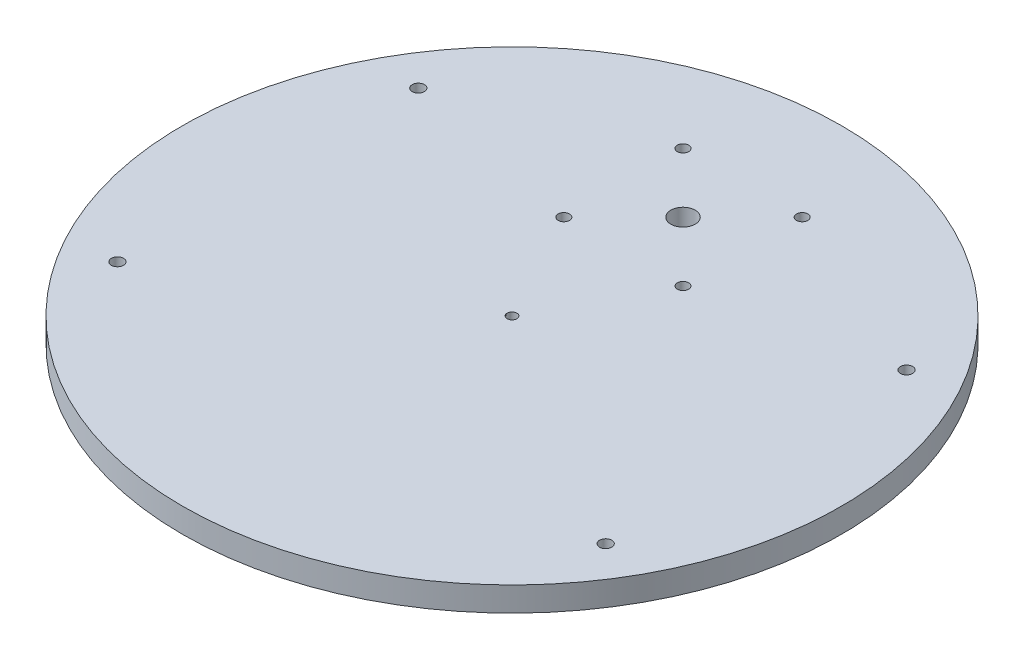
SolidWorks part; units mm, degrees
ref_plane "Front Plane" through (0, 0, 0) normal (0, 0, 1) x (1, 0, 0)
ref_plane "Top Plane" through (0, 0, 0) normal (0, 1, 0) x (1, 0, 0)
ref_plane "Right Plane" through (0, 0, 0) normal (1, 0, 0) x (0, 0, -1)
sketch "Sketch1" plane through (0, 0, 0) normal (0, 1, 0) x (1, 0, 0)
  circle A0 centre (0, 0) radius 85.725
  dimension "D1" = 171.45
extrude "Boss-Extrude1" add sketch "Sketch1" along normal blind 6.35
sketch "Sketch2" plane through (0, 6.35, 0) normal (0, 1, 0) x (1, 0, 0)
  line L0 (-63.5, 39.1325) -> (-63.5, -39.1325) construction
  line L1 (-63.5, -39.1325) -> (63.5, -39.1325) construction
  line L2 (63.5, -39.1325) -> (63.5, 39.1325) construction
  line L3 (63.5, 39.1325) -> (-63.5, 39.1325) construction
  circle A0 centre (-63.5, 39.1325) radius 1.5875
  circle A1 centre (63.5, 39.1325) radius 1.5875
  circle A2 centre (-63.5, -39.1325) radius 1.5875
  circle A3 centre (63.5, -39.1325) radius 1.5875
  dimension "D1" = 3.175
  dimension "D2" = 3.175
  dimension "D3" = 127
  dimension "D4" = 3.175
  dimension "D5" = 3.175
  dimension "D6" = 78.265
  dimension "D8" = 39.1325
  dimension "D9" = 63.5
extrude "Cut-Extrude1" cut sketch "Sketch2" against normal up to next
sketch "Sketch3" plane through (0, 6.35, 0) normal (0, 1, 0) x (1, 0, 0)
  line L0 (0, 44.4822) -> (0, 0) construction
  circle A0 centre (0, 44.4822) radius 3.175
  dimension "D1" = 6.35
  dimension "D2" = 44.4822
extrude "Cut-Extrude2" cut sketch "Sketch3" against normal up to next contours A0
ref_axis "Axis1" through (0, 6.35, 0) along (0, -1, 0)
sketch "Sketch5" plane through (0, 6.35, 0) normal (0, 1, 0) x (1, 0, 0)
  line L1 (-15.5004, 59.9825) -> (15.5003, 59.9825) construction
  line L2 (-15.5004, 59.9825) -> (-15.5003, 28.9818) construction
  line L3 (-15.5003, 28.9818) -> (15.5003, 28.9818) construction
  line L4 (15.5003, 59.9825) -> (15.5003, 28.9818) construction
  line L5 (-15.5004, 59.9825) -> (15.5003, 28.9818) construction
  line L6 (-15.5003, 28.9818) -> (15.5003, 59.9825) construction
  circle A0 centre (0, 44.4822) radius 3.175 construction
  circle A1 centre (0, 44.4822) radius 3.175 construction
  circle A2 centre (-15.5004, 59.9825) radius 1.4732
  circle A3 centre (15.5003, 59.9825) radius 1.4732
  circle A4 centre (-15.5003, 28.9818) radius 1.4732
  circle A5 centre (15.5003, 28.9818) radius 1.4732
  dimension "D3" = 2.9464
  dimension "D4" = 2.9464
  dimension "D5" = 2.9464
  dimension "D6" = 2.9464
  dimension "D1" = 31.0007
  dimension "D2" = 31.0007
extrude "Cut-Extrude3" cut sketch "Sketch5" against normal up to next
sketch "Sketch6" plane through (0, 6.35, 0) normal (0, 1, 0) x (1, 0, 0)
  circle A0 centre (0, 0) radius 1.27
  dimension "D1" = 2.54
extrude "center_hole" cut sketch "Sketch6" against normal up to next
